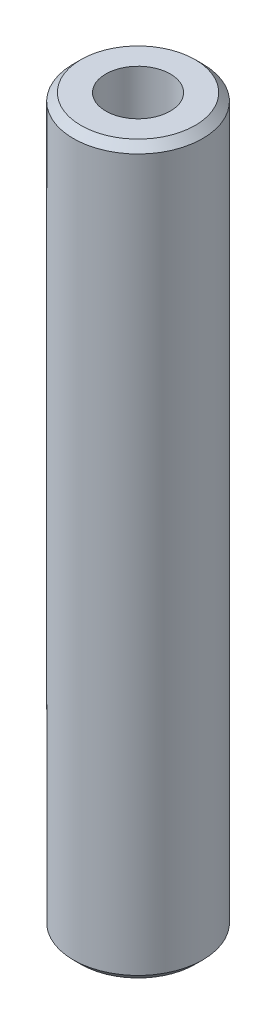
SolidWorks part; units mm, degrees
ref_plane "Front Plane" through (0, 0, 0) normal (0, 0, 1) x (1, 0, 0)
ref_plane "Top Plane" through (0, 0, 0) normal (0, 1, 0) x (1, 0, 0)
ref_plane "Right Plane" through (0, 0, 0) normal (1, 0, 0) x (0, 0, -1)
sketch "Sketch1" plane through (0, 0, 0) normal (0, 1, 0) x (1, 0, 0)
  circle A0 centre (0, 0) radius 32.5
  dimension "SHAFT_OD" = 65
extrude "Boss-Extrude1" add sketch "Sketch1" along normal blind 365.2646
sketch "Sketch2" plane through (0, 0, 0) normal (0, 1, 0) x (1, 0, 0)
  circle A0 centre (0, 0) radius 16.206
  dimension "BORE_D" = 32.4121
extrude "Cut-Extrude1" cut sketch "Sketch2" along normal through all
chamfer "Chamfer1" distance 3.7988 angle 45 2 edges at (0, 365.2646, 32.5) (0, 0, 32.5)
